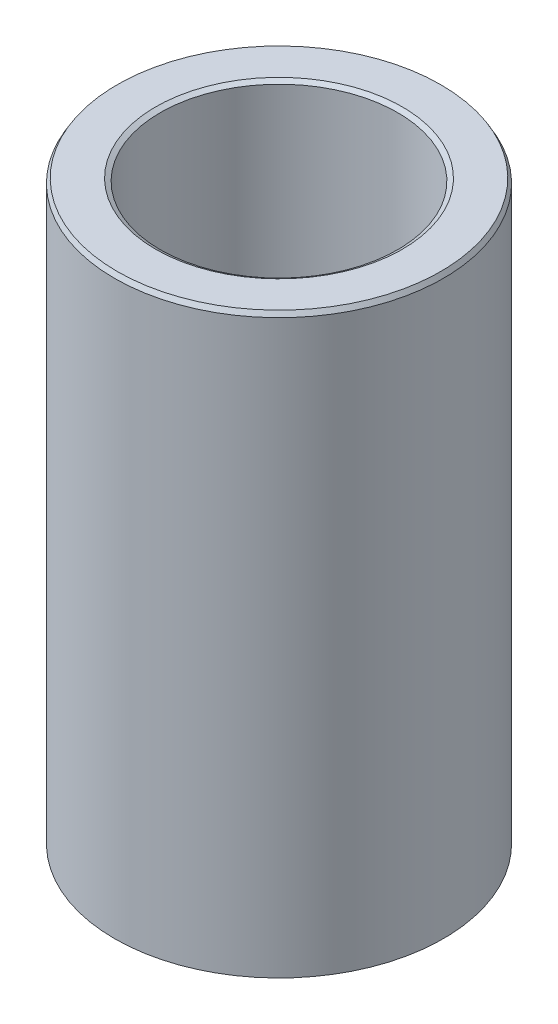
SolidWorks part; units mm, degrees
ref_plane "Front Plane" through (0, 0, 0) normal (0, 0, 1) x (1, 0, 0)
ref_plane "Top Plane" through (0, 0, 0) normal (0, 1, 0) x (1, 0, 0)
ref_plane "Right Plane" through (0, 0, 0) normal (1, 0, 0) x (0, 0, -1)
sketch "Sketch1" plane through (0, 0, 0) normal (0, 1, 0) x (1, 0, 0)
  circle A0 centre (0, 0) radius 47.5
  dimension "SLEEVE_OD" = 95
extrude "Boss-Extrude1" add sketch "Sketch1" along normal blind 167.2711
sketch "Sketch2" plane through (0, 0, 0) normal (0, 1, 0) x (1, 0, 0)
  circle A0 centre (0, 0) radius 34.2974
  dimension "BORE_D" = 68.5947
extrude "Cut-Extrude1" cut sketch "Sketch2" along normal through all
chamfer "Chamfer1" distance 1.3359 angle 30 4 edges at (0, 167.2711, 34.2974) (0, 0, 34.2974) (0, 0, 47.5) (0, 167.2711, 47.5) first distance on face at (0, 167.2711, 34.2974) first distance on face at (0, 0, 34.2974) first distance on face at (0, 167.2711, 47.5)
